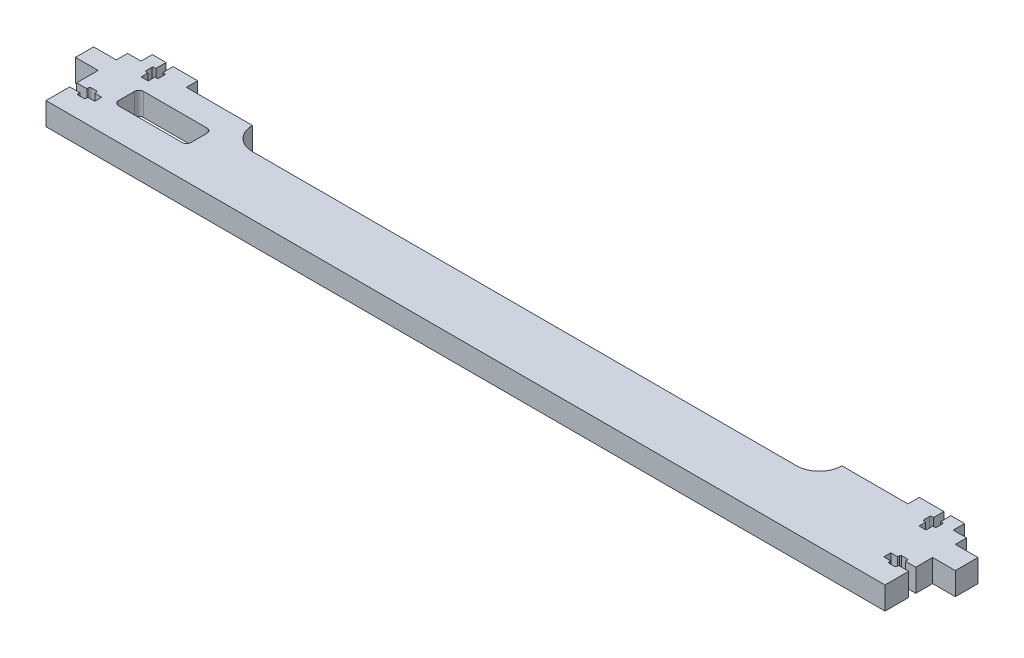
SolidWorks part; units mm, degrees
ref_plane "Front Plane" through (0, 0, 0) normal (0, 0, 1) x (1, 0, 0)
ref_plane "Top Plane" through (0, 0, 0) normal (0, 1, 0) x (1, 0, 0)
ref_plane "Right Plane" through (0, 0, 0) normal (1, 0, 0) x (0, 0, -1)
sketch "Sketch1" plane through (0, 0, 0) normal (0, 1, 0) x (1, 0, 0)
  line L0 (0, 18) -> (0, -18) construction
  line L1 (-185, 18) -> (0, 18)
  line L2 (-185, 18) -> (-185, 13)
  line L3 (-185, -18) -> (0, -18)
  line L4 (0, 18) -> (0, -18)
  line L5 (-185, 18) -> (0, 0) construction
  line L6 (-185, -18) -> (0, 0) construction
  line L7 (-185, 13) -> (-195, 13)
  line L8 (-195, 13) -> (-195, 3)
  line L9 (-195, 3) -> (-185, 3)
  line L10 (-185, 3) -> (-185, -18)
  point P0 (0, 0)
  dimension "D6" = 10
  dimension "D7" = 10
  dimension "D1" = 185
  dimension "D2" = 36
  dimension "D4" = 5
  dimension "D9" = 18
extrude "MainShape" add sketch "Sketch1" along normal blind 10 contours L2 L7 L8 L9 region at (-93.9423, 0, -0.1183)
sketch "Sketch15" plane through (0, 10, 0) normal (0, 1, 0) x (1, 0, 0)
  line L0 (-185, 18) -> (0, 18) construction
  line L1 (-159.1, 23) -> (-179.1, 23)
  line L2 (-159.1, 23) -> (-159.1, 13)
  line L3 (-159.1, 13) -> (-179.1, 13)
  line L4 (-179.1, 23) -> (-179.1, 13)
  line L5 (-159.1, 23) -> (-179.1, 13) construction
  line L6 (-159.1, 13) -> (-179.1, 23) construction
  line L7 (-185, 18) -> (-185, 13) construction
  point P0 (-169.1, 18)
  dimension "D1" = 20
  dimension "D2" = 5
  dimension "D3" = 15.9
extrude "Boss-Extrude4" add sketch "Sketch15" against normal through all
sketch "Sketch2" plane through (0, 10, 0) normal (0, 1, 0) x (1, 0, 0)
  line L0 (-171.5, 23) -> (-171.5, 12) construction
  line L2 (-173.05, 23) -> (-173.05, 18.5)
  line L3 (-173.05, 18.5) -> (-173.85, 18.5)
  line L4 (-174.35, 18) -> (-174.35, 15.5)
  line L5 (-173.85, 15) -> (-173.05, 15)
  line L6 (-173.05, 15) -> (-173.05, 12)
  line L7 (-173.05, 12) -> (-169.95, 12)
  line L8 (-185, 18) -> (-185, 13) construction
  line L9 (-173.05, 23) -> (-169.95, 23)
  line L10 (-169.95, 15) -> (-169.95, 12)
  line L11 (-169.15, 15) -> (-169.95, 15)
  line L12 (-168.65, 18) -> (-168.65, 15.5)
  line L13 (-169.95, 18.5) -> (-169.15, 18.5)
  line L14 (-169.95, 23) -> (-169.95, 18.5)
  line L16 (-185, -6) -> (-174, -6) construction
  line L17 (-159.1, 23) -> (-179.1, 23) construction
  line L50 (-185, 3) -> (-185, -18) construction
  line L51 (-174, -7.55) -> (-174, -4.45)
  line L52 (-174, -4.45) -> (-177, -4.45)
  line L53 (-177, -4.45) -> (-177, -3.65)
  line L54 (-177.5, -3.15) -> (-180, -3.15)
  line L55 (-180.5, -3.65) -> (-180.5, -4.45)
  line L56 (-180.5, -4.45) -> (-185, -4.45)
  line L57 (-185, -4.45) -> (-185, -7.55)
  line L58 (-195, 13) -> (-195, 3) construction
  line L59 (-180.5, -7.55) -> (-185, -7.55)
  line L60 (-180.5, -8.35) -> (-180.5, -7.55)
  line L61 (-177.5, -8.85) -> (-180, -8.85)
  line L62 (-177, -7.55) -> (-177, -8.35)
  line L63 (-174, -7.55) -> (-177, -7.55)
  arc A0 (-174.35, 15.5) -> (-173.85, 15) centre (-173.85, 15.5) ccw
  arc A1 (-173.85, 18.5) -> (-174.35, 18) centre (-173.85, 18) ccw
  arc A2 (-169.15, 18.5) -> (-168.65, 18) centre (-169.15, 18) cw
  arc A3 (-168.65, 15.5) -> (-169.15, 15) centre (-169.15, 15.5) cw
  arc A16 (-177, -3.65) -> (-177.5, -3.15) centre (-177.5, -3.65) ccw
  arc A17 (-180, -3.15) -> (-180.5, -3.65) centre (-180, -3.65) ccw
  arc A18 (-180, -8.85) -> (-180.5, -8.35) centre (-180, -8.35) cw
  arc A19 (-177, -8.35) -> (-177.5, -8.85) centre (-177.5, -8.35) cw
  point P14 (-174.35, 15)
  point P17 (-174.35, 18.5)
  point P28 (-168.65, 18.5)
  point P29 (-168.65, 15)
  point P34 (-195, 8)
  point P45 (-177, -3.15)
  point P48 (-180.5, -3.15)
  dimension "D8" = 0.5
  dimension "D16" = 0.5
  dimension "D1" = 11
  dimension "D2" = 1.55
  dimension "D3" = 1.55
  dimension "D5" = 2.85
  dimension "D6" = 3.5
  dimension "D7" = 13.5
  dimension "D9" = 11
  dimension "D10" = 8
  dimension "D11" = 3.5
  dimension "D12" = 2.85
  dimension "D13" = 1.55
  dimension "D14" = 1.55
  dimension "D15" = 14
  dimension "D4" = 8
extrude "ScrewSlots" cut sketch "Sketch2" against normal through all
mirror "Mirror1" about plane through (0, 0, 0) normal (1, 0, 0) of "Boss-Extrude4", "ScrewSlots", "MainShape"
sketch "Sketch6" plane through (0, 10, 0) normal (0, 1, 0) x (1, 0, 0)
  line L0 (0, -18) -> (0, -48) construction
  line L2 (-185, -18) -> (185, -18) construction
  line L3 (90, -48) -> (-90, -48)
  line L4 (-90, -48) -> (-120, -18)
  line L5 (90, -48) -> (120, -18)
  line L6 (-120, -18) -> (120, -18)
  dimension "D1" = 135
  dimension "D2" = 30
  dimension "D3" = 90
extrude "Boss-Extrude1" [suppressed] add sketch "Sketch6" against normal through all
sketch "Sketch8" plane through (0, 10, 0) normal (0, 1, 0) x (1, 0, 0)
  line L0 (-71.5, 4.8833) -> (-77.5, 4.8833) construction
  line L1 (-77, -1.6167) -> (-72, -1.6167)
  line L2 (-78, -0.6167) -> (-78, 4.3833)
  line L3 (-77, 5.3833) -> (-72, 5.3833)
  line L4 (-71, -0.6167) -> (-71, 4.3833)
  line L5 (-78, -1.6167) -> (-71, 5.3833) construction
  line L6 (-78, 5.3833) -> (-71, -1.6167) construction
  line L7 (-71.5, -1.1167) -> (-71.5, 4.8833) construction
  circle A0 centre (-74.5, -34.7667) radius 6.5
  circle A1 centre (-74.5, -15.8167) radius 5.5
  arc A2 (-77, -1.6167) -> (-78, -0.6167) centre (-77, -0.6167) cw
  circle A3 centre (-74.5, -34.7667) radius 6 construction
  circle A4 centre (-74.5, -15.8167) radius 3.5 construction
  arc A5 (-72, -1.6167) -> (-71, -0.6167) centre (-72, -0.6167) ccw
  arc A6 (-72, 5.3833) -> (-71, 4.3833) centre (-72, 4.3833) cw
  arc A7 (-78, 4.3833) -> (-77, 5.3833) centre (-77, 4.3833) cw
  point P6 (-74.5, 1.8833)
  dimension "D1" = 0.5
  dimension "D2" = 2
  dimension "D3" = 0.5
  dimension "D5" = 1
  dimension "D4" = 0.5
extrude "Cut-Extrude2" [suppressed] cut sketch "Sketch8" against normal through all
sketch "Sketch7" plane through (0, 10, 0) normal (0, 1, 0) x (1, 0, 0)
  circle A0 centre (60.5, -43.0167) radius 1.45
  circle A1 centre (-84.5, -43.0167) radius 1.45
  circle A2 centre (-84.5, 6.4833) radius 1.45
  circle A3 centre (60.5, 6.4833) radius 1.45
  dimension "D1" = 2.9
  dimension "D2" = 2.9
  dimension "D3" = 2.9
  dimension "D4" = 2.9
extrude "Cut-Extrude1" [suppressed] cut sketch "Sketch7" against normal through all
sketch "Sketch9" plane through (0, 10, 0) normal (0, 1, 0) x (1, 0, 0)
  line L0 (0, 7.2333) -> (0, -32.7667) construction
  line L1 (48.5, 7.2333) -> (-48.5, 7.2333) construction
  line L2 (-48.5, -32.7667) -> (48.5, -32.7667) construction
  line L3 (-48.5, -12.7667) -> (48.5, -12.7667) construction
  line L4 (-48.5, 7.2333) -> (-48.5, -32.7667) construction
  line L5 (48.5, -32.7667) -> (48.5, 7.2333) construction
  line L7 (-49, -33.2667) -> (49, -33.2667)
  line L8 (-49, -33.2667) -> (-49, 7.7333)
  line L9 (-49, 7.7333) -> (49, 7.7333)
  line L10 (49, -33.2667) -> (49, 7.7333)
  line L11 (-49, -33.2667) -> (49, 7.7333) construction
  line L12 (-49, 7.7333) -> (49, -33.2667) construction
  point P12 (0, -12.7667)
  dimension "D1" = 0.5
  dimension "D2" = 0.5
extrude "Cut-Extrude3" [suppressed] cut sketch "Sketch9" against normal through all and the other way through all
sketch "Sketch10" plane through (0, 10, 0) normal (0, 1, 0) x (1, 0, 0)
  line L0 (20, -39.2667) -> (20, -40.7667) construction
  line L1 (40, -39.2667) -> (0, -39.2667) construction
  line L2 (0, -40.7667) -> (40, -40.7667) construction
  line L3 (0, -40.0167) -> (40, -40.0167) construction
  line L4 (0, -39.2667) -> (0, -40.7667) construction
  line L5 (40, -40.7667) -> (40, -39.2667) construction
  line L7 (-0.2, -40.9667) -> (40.2, -40.9667)
  line L8 (-0.2, -40.9667) -> (-0.2, -39.0667)
  line L9 (-0.2, -39.0667) -> (40.2, -39.0667)
  line L10 (40.2, -40.9667) -> (40.2, -39.0667)
  line L11 (-0.2, -40.9667) -> (40.2, -39.0667) construction
  line L12 (-0.2, -39.0667) -> (40.2, -40.9667) construction
  point P12 (20, -40.0167)
  dimension "D1" = 0.2
  dimension "D2" = 0.2
extrude "Cut-Extrude4" [suppressed] cut sketch "Sketch10" against normal through all
sketch "Sketch12" [suppressed] plane through (0, 0, 0) normal (0, -1, 0) x (-1, 0, 0)
  line L1 (81.4, -9.8167) -> (67.6, -9.8167)
  line L2 (81.4, -9.8167) -> (81.4, -21.8167)
  line L3 (81.4, -21.8167) -> (67.6, -21.8167)
  line L4 (67.6, -9.8167) -> (67.6, -21.8167)
  line L5 (81.4, -9.8167) -> (67.6, -21.8167) construction
  line L6 (81.4, -21.8167) -> (67.6, -9.8167) construction
  point P0 (74.5, -15.8167)
  dimension "D1" = 13.8
  dimension "D2" = 12
extrude "PotentiometerAdjustment" [suppressed] cut sketch "Sketch12" against normal through all
sketch "Sketch11" plane through (0, 0, 0) normal (0, -1, 0) x (1, 0, 0)
  line L1 (-139, -7) -> (-167, -7)
  line L2 (-137, -5) -> (-137, 2)
  line L3 (-139, 4) -> (-167, 4)
  line L4 (-169, -5) -> (-169, 2)
  line L5 (-137, -7) -> (-169, 4) construction
  line L6 (-137, 4) -> (-169, -7) construction
  line L7 (173.05, -12) -> (169.95, -12) construction
  line L8 (-174, 7.55) -> (-174, 4.45) construction
  arc A0 (-137, 2) -> (-139, 4) centre (-139, 2) ccw
  arc A1 (-167, 4) -> (-169, 2) centre (-167, 2) ccw
  arc A2 (-167, -7) -> (-169, -5) centre (-167, -5) cw
  arc A3 (-139, -7) -> (-137, -5) centre (-139, -5) ccw
  point P0 (-153, -1.5)
  dimension "D3" = 2
  dimension "D1" = 32
  dimension "D2" = 11
  dimension "D4" = 5
  dimension "D5" = 5
extrude "LCDCableCutout" cut sketch "Sketch11" against normal through all
sketch "Sketch13" plane through (0, 10, 0) normal (0, 1, 0) x (1, 0, 0)
  line L0 (0, 18) -> (0, -18) construction
  line L1 (-169.95, 18) -> (169.95, 18) construction
  line L2 (-185, -18) -> (185, -18) construction
  line L3 (120, 18) -> (-120, 18) construction
  line L4 (120, 8) -> (-120, 8)
  line L5 (120, 28) -> (-120, 28)
  arc A0 (120, 8) -> (120, 28) centre (120, 18) ccw
  arc A1 (-120, 28) -> (-120, 8) centre (-120, 18) ccw
  point P8 (0, 18)
  dimension "D2" = 120
  dimension "D1" = 10
extrude "Cut-Extrude5" cut sketch "Sketch13" against normal through all
sketch "Sketch14" plane through (0, 10, 0) normal (0, 1, 0) x (1, 0, 0)
  line L1 (-169.95, 18) -> (169.95, 18) construction
  line L3 (-156.5, 18) -> (-156.5, 28) construction
  line L4 (-161.5, 18) -> (-151.5, 18)
  line L5 (-161.5, 18) -> (-161.5, 28)
  line L6 (-161.5, 28) -> (-151.5, 28)
  line L7 (-151.5, 18) -> (-151.5, 28)
  line L8 (-173.05, 12) -> (-169.95, 12) construction
  line L9 (154, 18) -> (154, 28) construction
  line L10 (149, 18) -> (149, 28)
  line L11 (159, 28) -> (149, 28)
  line L12 (159, 18) -> (159, 28)
  line L13 (159, 18) -> (149, 18)
  point P12 (-171.5, 12)
  dimension "D1" = 10
  dimension "D2" = 10
  dimension "D3" = 15
extrude "Boss-Extrude3" [suppressed] add sketch "Sketch14" against normal through all
sketch "Sketch16" plane through (0, 0, 0) normal (0, -1, 0) x (-1, 0, 0)
  line L0 (195, 13) -> (195, 3) construction
  line L1 (185, 3) -> (195, 3)
  line L2 (185, 3) -> (185, 5)
  line L3 (185, 5) -> (195, 5)
  line L4 (195, 3) -> (195, 5)
  dimension "D1" = 2
extrude "Cut-Extrude6" cut sketch "Sketch16" against normal through all
sketch "Sketch17" [suppressed] plane through (0, 0, 0) normal (0, -1, 0) x (-1, 0, 0)
  line L0 (-195, 13) -> (-195, 3) construction
  line L1 (-185, 3) -> (-195, 3)
  line L2 (-185, 3) -> (-185, 5)
  line L3 (-185, 5) -> (-195, 5)
  line L4 (-195, 3) -> (-195, 5)
  dimension "D1" = 2
extrude "Cut-Extrude7" [suppressed] cut sketch "Sketch17" against normal through all
equation "\"Y-ROD-SPACING\"=75"
equation "\"Y-BED-OFFSET\"=2"
equation "\"Y-BED-ROD-INSET\"=3.5"
equation "\"T-SLOT-NUT-FILLET-RADIUS\"=0.5"
equation "\"T-SLOT-SCREW-SHAFT-RADIUS\"=1.55"
equation "\"T-SLOT-SCREW-SHAFT-CUTOUT-LENGTH\"=11"
equation "\"T-SLOT-NUT-DEPTH\"=3.5"
equation "\"T-SLOT-NUT-WIDTH\"=2.85"
equation "\"T-SLOT-NUT-END-DISTANCE\"=8"
equation "\"ACRYLIC-TAB-CUTOUT-SIZE\"=\"ACRYLIC-THICKNESS\"+\"ACRYLIC-TAB-TOLERANCE\"*2"
equation "\"ACRYLIC-M3-HOLE\"=2.9"
equation "\"SMOOTHROD-CAP-SCREW-DISTANCE\"=20"
equation "\"D2@Sketch2\"=\"T-SLOT-SCREW-SHAFT-RADIUS\""
equation "\"D1@Sketch2\"=\"T-SLOT-SCREW-SHAFT-CUTOUT-LENGTH\""
equation "\"D6@Sketch2\"=\"T-SLOT-NUT-DEPTH\""
equation "\"D5@Sketch2\"=\"T-SLOT-NUT-WIDTH\""
equation "\"D3@Sketch2\"=\"T-SLOT-SCREW-SHAFT-RADIUS\""
equation "\"D8@Sketch2\"=\"T-SLOT-NUT-FILLET-RADIUS\""
equation "\"D4@Sketch2\"=\"T-SLOT-NUT-END-DISTANCE\""
equation "\"D11@Sketch2\"=\"T-SLOT-NUT-DEPTH\""
equation "\"D10@Sketch2\"=\"T-SLOT-NUT-END-DISTANCE\""
equation "\"D13@Sketch2\"=\"T-SLOT-SCREW-SHAFT-RADIUS\""
equation "\"D14@Sketch2\"=\"T-SLOT-SCREW-SHAFT-RADIUS\""
equation "\"D16@Sketch2\"=\"T-SLOT-NUT-FILLET-RADIUS\""
equation "\"D9@Sketch2\"=\"T-SLOT-SCREW-SHAFT-CUTOUT-LENGTH\""
equation "\"ACRYLIC-TAB-WIDTH\"=\"ACRYLIC-THICKNESS\""
equation "\"D6@Sketch1\"=\"ACRYLIC-TAB-WIDTH\""
equation "\"D7@Sketch1\"=\"ACRYLIC-TAB-WIDTH\""
equation "\"FRAME-WIDTH-INNER\"=370"
equation "\"D1@Sketch1\"=\"FRAME-WIDTH-INNER\"/2"
equation "\"X-ROD-SPACING\"=45"
equation "\"Z-ROD-SPACING\"=17.5"
equation "\"ACRYLIC-THICKNESS\"=10"
equation "\"ACRYLIC-THICKNESS2\"=4.5"
equation "\"NEMA17-HOLE-SPACING\"=31"
equation "\"NEMA17-CENTRAL-CUTOUT\"=22.5"
equation "\"Z-BRACKET-REACH\"=57"
equation "\"TOP-BRACKET-SPACING\"=40"
equation "\"SMOOTHROD-X-LENGTH\"=350"
equation "\"SMOOTHROD-Y-LENGTH\"=350"
equation "\"SMOOTHROD-Z-LENGTH\"=350"
equation "\"SMOOTHROD-TIGHTENING-HEADROOM\"=.25"
equation "\"LEADSCREW-Z-LENGTH\"=300"
equation "\"SCREW-LENGTH-FRAME\"=\"ACRYLIC-THICKNESS\" + 10"
equation "\"SCREW-HEAD-RADIUS\"=6"
equation "\"PRINTED-X-SMOOTHROD-DIAMETER\"=8.8"
equation "\"PRINTED-X-SMOOTHROD-CUTOUT\"=10"
equation "\"PRINTED-X-BASE-HEIGHT\"=10"
equation "\"PRINTED-LM8UU-CUTOUT-SIZE\"=15.5"
equation "\"PRINTED-LM8UU-CUTOUT-LENGTH\"=24.5"
equation "\"PRINTED-X-IDLER-HEIGHT\"=16"
equation "\"PSU-MOUNTING-WIDTH\"=50"
equation "\"PSU-MOUNTING-HEIGHT\"=150"
equation "\"D1@MainShape\"=\"ACRYLIC-THICKNESS\""
equation "\"Y-BELT-TO-ROD-DISTANCE\"=20"
equation "\"SPOOL-HOLDER-ROD-SPACING\"=150"
equation "\"Z-ROD-INSET\"=13.5"
equation "\"D7@Sketch2\"=\"Z-ROD-INSET\""
equation "\"D1@Sketch7\"=\"ACRYLIC-M3-HOLE\""
equation "\"D2@Sketch7\"=\"ACRYLIC-M3-HOLE\""
equation "\"D3@Sketch7\"=\"ACRYLIC-M3-HOLE\""
equation "\"D4@Sketch7\"=\"ACRYLIC-M3-HOLE\""
equation "\"Y-BED-SCREW-SPACING\"=209"
equation "\"Y-BED-SCREW-CUTOUT-SLOT-HEIGHT\"=2.5"
equation "\"ACRYLIC-TAB-TOLERANCE\"=-.05"
equation "\"SCREW-LENGTH-MOTOR\"=\"ACRYLIC-THICKNESS\" + 5"
equation "\"SCREW-LENGTH-EXTRUDER\"=28"
equation "\"PRINTED-M3-HOLE\"=3.5"
equation "\"PRINTED-M3-NUT-AF\"=6.25"
equation "\"ACRYLIC-X-CARRIAGE-WIDTH\"=55"
equation "\"ACRYLIC-X-CARRIAGE-HEIGHT\"=75"
equation "\"ACRYLIC-X-CARRIAGE-LM8UU-CUTOUT-WIDTH\"=24.25"
equation "\"ACRYLIC-X-CARRIAGE-LM8UU-CUTOUT-HEIGHT\"=11.0"
equation "\"ACRYLIC-X-CARRIAGE-SCREW-SPACING-X\"=15"
equation "\"ACRYLIC-X-CARRIAGE-SCREW-SPACING-Y\"=33"
equation "\"ACRYLIC-X-CARRIAGE-CENTER-TAB-SPACING\"=14"
equation "\"ACRYLIC-X-CARRIAGE-EXTRUDER-OFFSET\"=26"
equation "\"ACRYLIC-X-CARRIAGE-EXTRUDER-ANGLE\"=90"
equation "\"ACRYLIC-X-CARRIAGE-EXTRUDER-SHELF-DEPTH\"=\"ACRYLIC-X-CARRIAGE-EXTRUDER-OFFSET\" + 28"
equation "\"ACRYLIC-X-CARRIAGE-EXTRUDER-BRACE-SPACING\"=23"
equation "\"ACRYLIC-X-CARRIAGE-EXTRUDER-BRACE-TAB-OFFSET\"=20"
equation "\"ACRYLIC-X-CARRIAGE-EXTRUDER-BRACE-HEIGHT\"=35"
equation "\"ACRYLIC-X-CARRIAGE-EXTRUDER-BRACE-SCREW-SPACING\"=22"
equation "\"ACRYLIC-X-CARRIAGE-DUAL-WIDTH-MULTIPLIER\"=1.65"
equation "\"ACRYLIC-X-CARRIAGE-DUAL-HOTEND-SPACING\"=42"
equation "\"ACRYLIC-X-CARRIAGE-DUAL-WIDTH\"=75"
equation "\"ACRYLIC-X-CARRIAGE-DUAL-HOTEND-SEPARATION\"=36"
equation "\"ACRYLIC-X-CARRIAGE-DUAL-MOUNT-PLATE-DEPTH\"=75"
equation "\"ACRYLIC-X-CARRIAGE-DUAL-MOUNT-BRACE-WIDTH\"=33"
equation "\"ACRYLIC-X-CARRIAGE-DUAL-MOUNT-SCREW-WIDTH\"=40"
equation "\"BLOWER-FAN-WIDTH\"=15"
equation "\"D1@Sketch14\"=\"ACRYLIC-TAB-WIDTH\""
equation "\"D2@Sketch14\"=\"ACRYLIC-THICKNESS\""
equation "\"D3@Sketch15\"=\"Z-ROD-INSET\"+2.4"
equation "\"D12@Sketch2\"=\"T-SLOT-NUT-WIDTH\""
